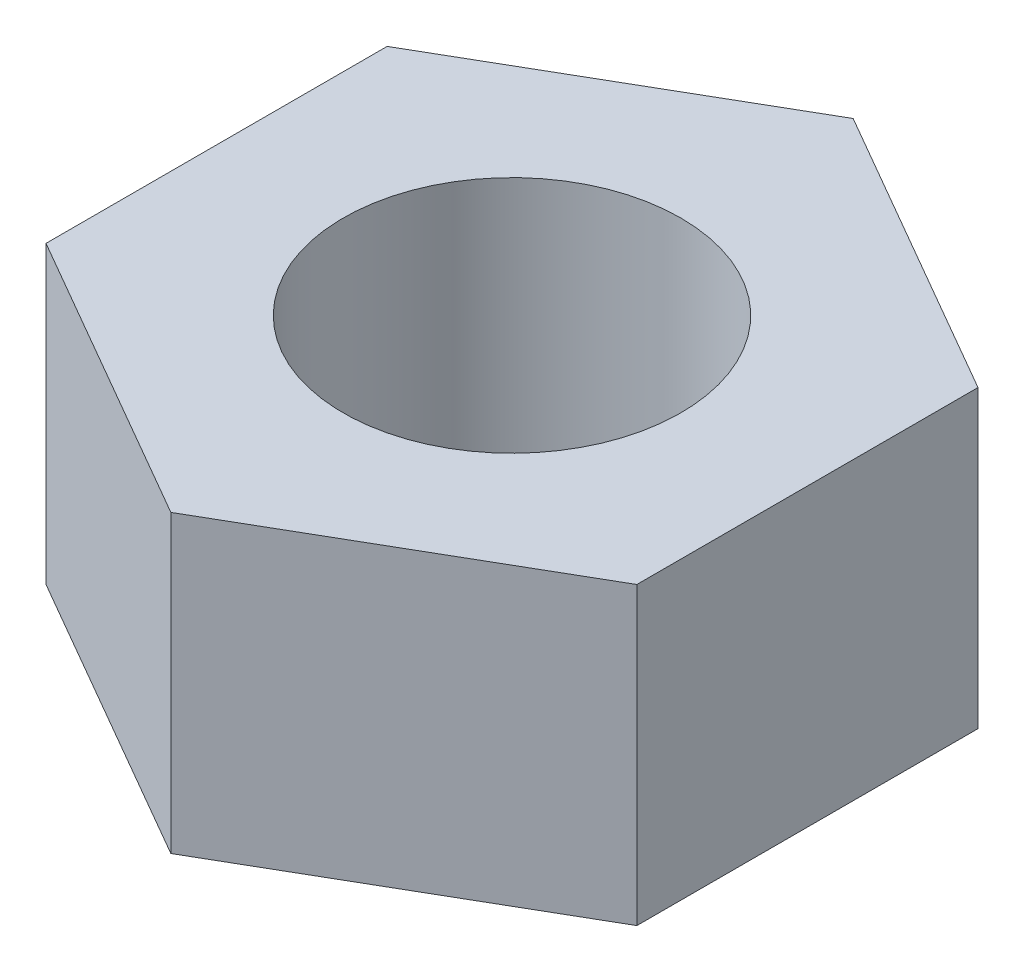
SolidWorks part; units mm, degrees
material "AISI 4130 Steel, normalized at 870C"
ref_plane "Front Plane" through (0, 0, 0) normal (0, 0, 1) x (1, 0, 0)
ref_plane "Top Plane" through (0, 0, 0) normal (0, 1, 0) x (1, 0, 0)
ref_plane "Right Plane" through (0, 0, 0) normal (1, 0, 0) x (0, 0, -1)
sketch "Sketch1" plane through (0, 0, 0) normal (0, 0, 1) x (1, 0, 0)
  line L0 (0, -2.7781) -> (0, 2.7781) construction
  line L1 (5.5562, 0) -> (-5.5562, 0) construction
  line L2 (3.175, -2.7781) -> (-3.175, -2.7781) construction
  line L3 (3.175, -2.7781) -> (3.175, -1.5081) construction
  point P4 (0, 0)
  point P8 (0, 0)
  point P11 (0, -2.7781)
  dimension "Height" = 5.5562
  dimension "Width" = 11.1125
  dimension "Thread Size" = 6.35
  dimension "Thread Pitch" = 1.27
sketch "Sketch2" plane through (0, 0, 0) normal (1, 0, 0) x (0, 0, -1)
  line L0 (0, -2.7781) -> (0, 2.7781) construction
  line L1 (3.048, -3.3433) -> (-3.048, -3.3433)
  line L2 (3.048, -3.3433) -> (3.048, 2.7781)
  line L3 (3.048, 2.7781) -> (-3.048, 2.7781)
  line L4 (-3.048, -3.3433) -> (-3.048, 2.7781)
  line L5 (3.048, -3.3433) -> (-3.048, 2.7781) construction
  line L6 (3.048, 2.7781) -> (-3.048, -3.3433) construction
  point P0 (0, -0.2826)
  point P7 (0, 2.7781)
  dimension "Minimum Slot Width" = 6.096
  dimension "Minimum Slot Depth" = 6.1214
sketch "Sketch11" plane through (0, 0, 0) normal (0, 1, 0) x (1, 0, 0)
  line L1 (0, 6.4158) -> (-5.5562, 3.2079)
  line L2 (-5.5562, 3.2079) -> (-5.5562, -3.2079)
  line L3 (-5.5562, -3.2079) -> (0, -6.4158)
  line L4 (0, -6.4158) -> (5.5562, -3.2079)
  line L5 (5.5562, -3.2079) -> (5.5562, 3.2079)
  line L6 (5.5562, 3.2079) -> (0, 6.4158)
  circle A0 centre (0, 0) radius 5.5563 construction
  circle A1 centre (0, 0) radius 3.175
  point P19 (0, -3.175)
extrude "Boss-Extrude1" add sketch "Sketch11" along normal up to vertex (2.7781 mm away) and the other way up to vertex (2.7781 mm away) up to point (0, 2.7781, 0) other way up to point (0, -2.7781, 0)
fillet "Fillet1" [suppressed] radius 0.3334
sketch "Sketch3" plane through (0, 0, 0) normal (1, 0, 0) x (0, 0, -1)
  line L1 (3.2079, 2.7781) -> (6.4158, 2.7781) construction
  line L2 (5.0006, -2.7781) -> (6.4158, -1.9611)
  line L3 (3.2079, -2.7781) -> (6.4158, -2.7781) construction
  line L4 (6.4158, 2.7781) -> (6.4158, -2.7781) construction
  line L5 (6.4158, -1.9611) -> (6.4158, -2.7781)
  line L7 (5.1118, 2.7781) -> (6.4158, 2.0252)
  line L8 (6.4158, 2.0252) -> (6.4158, 2.7781)
  line L10 (5.0006, -2.7781) -> (6.4158, -2.7781)
  line L12 (5.1118, 0) -> (5.5563, 0) construction
  line L16 (5.1118, 2.7781) -> (6.4158, 2.7781)
  line L21 (3.175, -2.7781) -> (3.175, -2.6194)
  line L22 (-3.2079, -2.7781) -> (3.2079, -2.7781) construction
  line L24 (3.3338, -2.7781) -> (3.175, -2.7781)
  line L25 (3.175, -2.6194) -> (3.3338, -2.7781)
  line L26 (3.175, 2.7781) -> (3.175, 2.6194)
  line L27 (3.175, 2.7781) -> (3.3338, 2.7781)
  line L28 (3.3338, 2.7781) -> (3.175, 2.6194)
  line L29 (3.048, 2.7781) -> (-3.048, 2.7781) construction
  line L30 (3.3338, 0) -> (3.7783, 0) construction
  line L31 (4.6673, 0) -> (5.1118, 0) construction
  line L32 (3.7783, 0) -> (4.2228, 0) construction
  line L33 (4.2228, 0) -> (4.6673, 0) construction
  point P0 (5.1118, 2.7781)
  point P1 (5.5563, 0)
  point P14 (3.175, 0)
  point P36 (5.5563, -2.7781)
  point P44 (5.334, 0)
  dimension "D2" = 30
  dimension "D5" = 0.1588
  dimension "D7" = 0.5556
  dimension "D1" = 30
revolve "Cut-Revolve2" [suppressed] cut sketch "Sketch3" angle 360 about L0
sketch "Sketch15" [suppressed] plane through (16.2719, 0, 15.8104) normal (0.5, 0, -0.866) x (-0.866, 0, -0.5)
  line L0 (21.997, 2.5215) -> (21.997, 1.2768) construction
  line L1 (21.997, -1.2126) -> (21.997, 0.0321) construction
  line L2 (21.997, 0.0321) -> (21.997, 1.2768) construction
  line L3 (21.997, -1.2126) -> (21.997, -2.4573) construction
  line L6 (21.2784, 0.0321) -> (21.6377, -0.5903)
  line L7 (21.6377, -0.5903) -> (22.3564, -0.5903)
  line L8 (22.3564, -0.5903) -> (22.7157, 0.0321)
  line L9 (22.7157, 0.0321) -> (22.3564, 0.6544)
  line L10 (22.3564, 0.6544) -> (21.6377, 0.6544)
  line L11 (21.6377, 0.6544) -> (21.2784, 0.0321)
  circle A0 centre (21.997, 0.0321) radius 0.6224 construction
  spline S4 degree 3 poles (18.7891, 2.0252) (19.8367, 2.3276) (20.9, 2.5208) (22.2636, 2.5217) (22.5377, 2.5101) (23.0797, 2.4648) (23.3489, 2.4312) (24.1517, 2.3016) (24.6805, 2.1766) (25.2049, 2.0252) knots 0 0 0 0 0.5 0.5 0.625 0.625 0.75 0.75 1 1 1 1 construction
  spline S5 degree 3 poles (25.2049, -1.9611) (24.1574, -2.2635) (23.0941, -2.4566) (21.7304, -2.4575) (21.4564, -2.4459) (20.9144, -2.4007) (20.6452, -2.3671) (19.8424, -2.2374) (19.3136, -2.1125) (18.7891, -1.9611) knots 0 0 0 0 0.5 0.5 0.625 0.625 0.75 0.75 1 1 1 1 construction
  point P1 (21.997, 0.6544)
  point P6 (21.997, 0)
extrude "Cut-Extrude2" [suppressed] cut sketch "Sketch15" along normal blind 0.1588
sketch "Sketch18" [suppressed] plane through (0, 2.7781, 0) normal (0, 1, 0) x (1, 0, 0)
  line L0 (0, 0) -> (0, -5.1118) construction
  line L1 (0, 0) -> (-2.9859, -2.9859) construction
  line L2 (0, 0) -> (-1.0929, -4.0789) construction
  line L3 (-5.1118, 0) -> (-4.7562, 0) construction
  line L4 (-4.7562, 0) -> (-4.4006, 0) construction
  line L5 (-4.4006, 0) -> (-4.045, 0) construction
  line L6 (-4.045, 0) -> (-3.6894, 0) construction
  line L7 (-3.6894, 0) -> (-3.3338, 0) construction
  line L8 (0, 0) -> (-2.7781, -4.8119) construction
  line L9 (-5.5562, -3.2079) -> (0, -6.4158) construction
  circle A0 centre (0, 0) radius 5.1118 construction
  circle A1 centre (0, 0) radius 3.3338 construction
  arc A2 (-2.9859, -2.9859) -> (-1.0929, -4.0789) centre (0, 0) ccw construction
  arc A3 (-3.1117, -3.1117) -> (-1.1389, -4.2506) centre (0, 0) ccw
  arc A4 (-2.8602, -2.8602) -> (-1.0469, -3.9071) centre (0, 0) ccw
  arc A5 (-2.8602, -2.8602) -> (-3.1117, -3.1117) centre (-2.9859, -2.9859) ccw
  arc A6 (-1.1389, -4.2506) -> (-1.0469, -3.9071) centre (-1.0929, -4.0789) ccw
  arc A7 (2.9859, -2.9859) -> (1.0929, -4.0789) centre (0, 0) cw construction
  arc A8 (3.1117, -3.1117) -> (1.1389, -4.2506) centre (0, 0) cw
  arc A9 (2.8602, -2.8602) -> (1.0469, -3.9071) centre (0, 0) cw
  arc A10 (2.8602, -2.8602) -> (3.1117, -3.1117) centre (2.9859, -2.9859) cw
  arc A11 (1.1389, -4.2506) -> (1.0469, -3.9071) centre (1.0929, -4.0789) cw
  point P18 (-2.1114, -3.657)
  point P30 (2.1114, -3.657)
  dimension "D1" = 30
extrude "Cut-Extrude3" [suppressed] cut sketch "Sketch18" against normal blind 0.1984
sketch "Sketch5" [suppressed] plane through (0, 0, 0) normal (0, 1, 0) x (1, 0, 0)
  circle A1 centre (0, 0) radius 3.175 construction
  point P0 (0, -3.175)
sketch "Sketch6" [suppressed] plane through (0, 0, 0) normal (0, 0, 1) x (1, 0, 0)
  line L0 (3.175, 2.7781) -> (3.175, -2.7781)
  line L2 (0, -2.7781) -> (5.5562, -2.7781) construction
  line L3 (3.175, -2.7781) -> (0, -2.7781)
  line L4 (0, -2.7781) -> (0, 2.7781)
  line L5 (0, -2.7781) -> (0, 2.7781) construction
  line L6 (0, 2.7781) -> (3.175, 2.7781)
revolve "Revolve2" [suppressed] add sketch "Sketch6" angle 360 about L4
sketch "Sketch7" [suppressed] plane through (0, -2.7781, 0) normal (0, -1, 0) x (1, 0, 0)
  circle A2 centre (0, 0) radius 3.175
  circle A3 centre (0, 0) radius 3.175
  dimension "D1" = 0
curve "Helix/Spiral1" [suppressed] pitch 1.27 height 5.5562 turns 4.375
sketch "Sketch8" [suppressed] plane through (0, 0, 0) normal (0, 0, 1) x (1, 0, 0)
  line L0 (3.3125, -2.6987) -> (2.2126, -3.3337) construction
  line L1 (2.2126, -3.3337) -> (3.3125, -3.9687) construction
  line L2 (3.3125, -3.9687) -> (3.3125, -2.6987) construction
  line L3 (2.3501, -3.2544) -> (2.3501, -3.4131)
  line L4 (3.175, -2.7781) -> (3.175, -3.8894) construction
  line L5 (3.175, -3.3337) -> (3.3125, -3.3337) construction
  line L6 (2.2126, -3.3337) -> (2.3501, -3.3337) construction
  line L7 (3.2437, -3.3337) -> (3.2437, -3.9291) construction
  line L8 (2.3501, -3.2544) -> (3.3125, -2.6987)
  line L9 (3.3125, -2.6987) -> (3.2437, -3.9291)
  line L10 (2.3501, -3.4131) -> (3.2437, -3.9291)
  dimension "D1" = 1.27
  dimension "D2" = 0.1588
sweep "Cut-Sweep1" [suppressed] cut profiles "Sketch8" path "Helix/Spiral1"
sketch "Sketch9" [suppressed] plane through (0, 0, 0) normal (0, 0, 1) x (1, 0, 0)
  line L0 (0, 0.3969) -> (0, -2.7781)
  line L1 (0, 0.3969) -> (0, 0.5556)
  line L2 (0, -2.7781) -> (3.175, -2.7781)
  line L3 (3.175, -2.7781) -> (3.3337, -2.7781)
  line L4 (3.3337, -2.7781) -> (0, 0.5556)
  dimension "D1" = 0.1588
revolve "Revolve3" [suppressed] add sketch "Sketch9" angle 360 about L0
sketch "Sketch14" [suppressed] plane through (0, 0, 0) normal (0, 0, 1) x (1, 0, 0)
  line L0 (3.3337, 2.7781) -> (0, 2.7781)
  line L1 (0, 2.7781) -> (0, -0.5556)
  line L2 (0, -0.5556) -> (3.3337, 2.7781)
revolve "Revolve4" [suppressed] add sketch "Sketch14" angle 360 about L1
sketch "Sketch10" [suppressed] plane through (0, -2.7781, 0) normal (0, -1, 0) x (1, 0, 0)
  circle A0 centre (0, 0) radius 3.3338 construction
  circle A1 centre (0, 0) radius 3.3338
extrude "Boss-Extrude2" [suppressed] add sketch "Sketch10" against normal up to surface (5.5563 mm away)
combine bodies "Combine1" [suppressed] operation type subtract main body 110 bodies to subtract 120
equation "\"D5@Sketch3\"=\"Thread Size@Sketch1\"*.025"
equation "\"D4@Helix/Spiral1\" = \"Thread Pitch@Sketch1\""
equation "\"D3@Helix/Spiral1\" = \"Height@Sketch1\""
equation "\"D1@Sketch8\" = \"Thread Pitch@Sketch1\""
equation "\"D2@Sketch8\" = \"Thread Pitch@Sketch1\" / 8"
equation "\"D1@Sketch9\"=\"Thread Size@Sketch1\" * .025"
equation "\"D1@Fillet1\"=\"Width@Sketch1\" * .03"
equation "\"D7@Sketch3\"=\"Width@Sketch1\"*.05"
equation "\"D1@Cut-Extrude2\" =  (  ( \"Width@Sketch1\" - \"Thread Size@Sketch1\" / 2 )  * .02 ) "
equation "\"D1@Cut-Extrude3\"=((\"width@sketch1\"-\"Thread Size@sketch1\"/2)*.025)"
